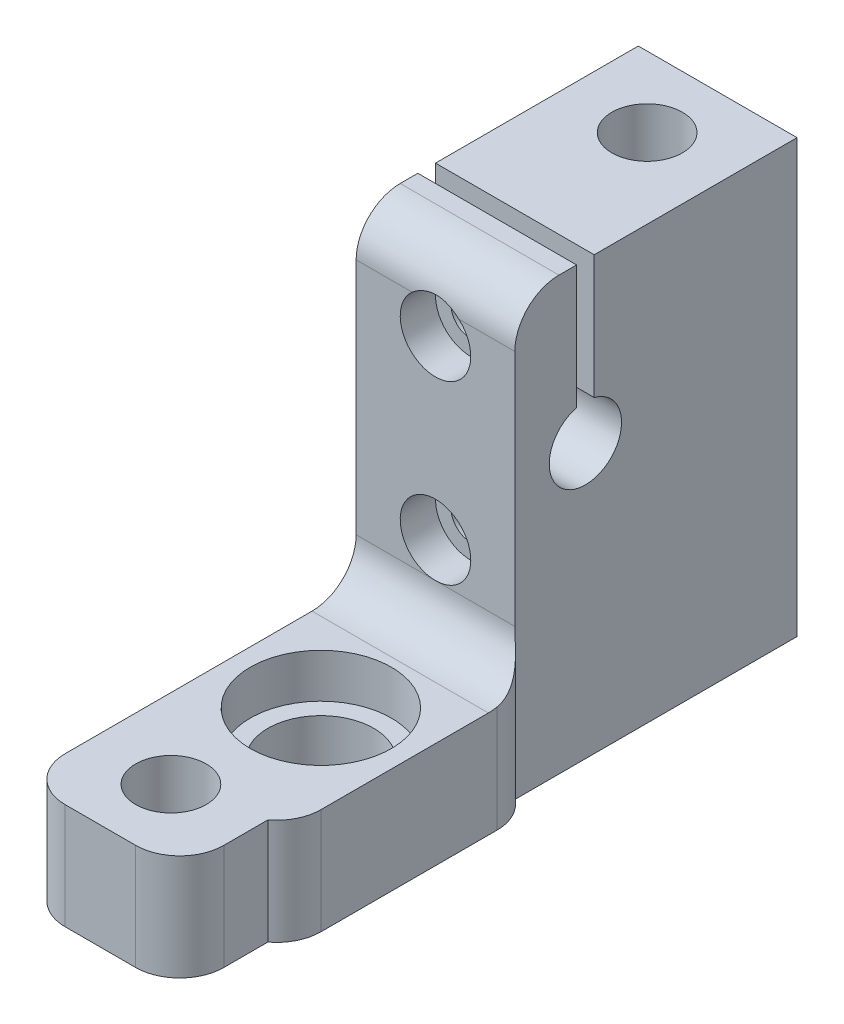
SolidWorks part; units mm, degrees
ref_plane "Спереди" through (0, 0, 0) normal (0, 0, 1) x (1, 0, 0)
ref_plane "Сверху" through (0, 0, 0) normal (0, 1, 0) x (1, 0, 0)
ref_plane "Справа" through (0, 0, 0) normal (1, 0, 0) x (0, 0, -1)
sketch "Эскиз2" plane through (0, 0, 0) normal (0, 1, 0) x (1, 0, 0)
  line L1 (-9, 16) -> (9, 16)
  line L2 (-9, 16) -> (-9, -16)
  line L3 (-9, -16) -> (9, -16)
  line L4 (9, 16) -> (9, -16)
  line L5 (-9, 16) -> (9, -16) construction
  line L6 (-9, -16) -> (9, 16) construction
  point P0 (0, 0)
  dimension "D1" = 32
  dimension "D2" = 18
extrude "Бобышка-Вытянуть1" add sketch "Эскиз2" along normal blind 49
sketch "Эскиз3" plane through (9, 0, -3.2795) normal (1, 0, 0) x (0, 0, -1)
  line L0 (12.7205, 49) -> (12.7205, 0) construction
  line L2 (-19.2795, 0) -> (12.7205, 0) construction
  circle A0 centre (-11.2795, 31) radius 4.1
  dimension "D1" = 8.2
  dimension "D2" = 31
  dimension "D3" = 24
extrude "Вырез-Вытянуть1" cut sketch "Эскиз3" against normal blind 27.3
sketch "Эскиз16" plane through (0, 0, 0) normal (0, -1, 0) x (1, 0, 0)
  line L1 (11, 16) -> (-9, 16)
  line L2 (11, 16) -> (11, 44)
  line L3 (11, 44) -> (-9, 44)
  line L4 (-9, 16) -> (-9, 44)
  dimension "D1" = 20
  dimension "D2" = 28
extrude "Бобышка-Вытянуть3" add sketch "Эскиз16" against normal blind 12
sketch "Эскиз17" plane through (0, 0, 16) normal (0, 0, 1) x (1, 0, 0)
  line L0 (-9, 49) -> (9, 49) construction
  circle A0 centre (0, 41) radius 2.25
  circle A1 centre (0, 21) radius 2.25
  point P5 (0, 49)
  dimension "D1" = 4.5
  dimension "D2" = 8
  dimension "D3" = 20
extrude "Вырез-Вытянуть3" cut sketch "Эскиз17" against normal blind 66
sketch "Эскиз18" plane through (0, 0, -16) normal (0, 0, -1) x (-1, 0, 0)
  line L1 (3, 5) -> (-3, 5)
  line L2 (3, 5) -> (3, 14)
  line L3 (3, 14) -> (-3, 14)
  line L4 (-3, 5) -> (-3, 14)
  line L5 (3, 28) -> (-3, 28)
  line L6 (3, 28) -> (3, 34)
  line L7 (3, 34) -> (-3, 34)
  line L8 (-3, 28) -> (-3, 34)
  line L9 (-9, 0) -> (9, 0) construction
  circle A0 centre (0, 21) radius 2.25 construction
  circle A1 centre (0, 41) radius 2.25 construction
  point P8 (0, 5)
  point P12 (0, 0)
  dimension "D1" = 6
  dimension "D2" = 5
  dimension "D3" = 7
  dimension "D4" = 7
  dimension "D5" = 7
extrude "Бобышка-Вытянуть4" add sketch "Эскиз18" along normal blind 4
sketch "Эскиз19" plane through (0, 0, 16) normal (0, 0, 1) x (1, 0, 0)
  circle A0 centre (0, 21) radius 4
  circle A1 centre (0, 41) radius 4
  dimension "D1" = 8
extrude "Вырез-Вытянуть4" cut sketch "Эскиз19" against normal blind 4
sketch "Эскиз20" plane through (0, 12, 0) normal (0, 1, 0) x (1, 0, 0)
  line L1 (9, 16) -> (-9, 16) construction
  line L2 (11, -16) -> (11, -44) construction
  circle A0 centre (1, -30) radius 8
  circle A1 centre (1, -30) radius 6
  dimension "D1" = 16
  dimension "D2" = 12
  dimension "D3" = 46
  dimension "D4" = 10
sketch "Эскиз23" plane through (0, 0, 0) normal (0, -1, 0) x (1, 0, 0)
  line L0 (-9, -16) -> (-9, 44) construction
  line L1 (9, 44) -> (-9, 44)
  line L2 (9, 44) -> (9, 54)
  line L3 (9, 54) -> (-9, 54)
  line L4 (-9, 44) -> (-9, 54)
  line L5 (9, 16) -> (9, -16) construction
  line L6 (11, 44) -> (-9, 44) construction
  dimension "D1" = 10
extrude "Бобышка-Вытянуть5" add sketch "Эскиз23" against normal up to surface (12 mm away) up to face at (2.6, 12, 27.2)
sketch "Эскиз4" plane through (0, 0, 0) normal (0, -1, 0) x (1, 0, 0)
  line L0 (9, -16) -> (-9, -16) construction
  line L2 (-9, 54) -> (9, 54) construction
  circle A0 centre (0, 46) radius 2.25
  circle A1 centre (0, -8) radius 2.25
  dimension "D3" = 4.5
  dimension "D1" = 8
  dimension "D2" = 8
extrude "Вырез-Вытянуть2" cut sketch "Эскиз4" against normal through all
sketch "Эскиз8" plane through (0, 0, 0) normal (0, -1, 0) x (1, 0, 0)
  line L0 (9, -16) -> (-9, -16) construction
  line L1 (-3, 0) -> (3, 0)
  line L2 (-3, 0) -> (-3, 38)
  line L3 (-3, 38) -> (3, 38)
  line L4 (3, 0) -> (3, 38)
  line L6 (3, 34.8874) -> (-3, 34.8874)
  line L7 (3, 34.8874) -> (3, 24.7217)
  line L8 (3, 24.7217) -> (-3, 24.7217)
  line L9 (-3, 34.8874) -> (-3, 24.7217)
  circle A0 centre (0, -8) radius 2.25 construction
  circle A1 centre (0, 46) radius 2.25 construction
  point P0 (0, -11.3393)
  point P6 (0, 0)
  point P9 (0, -16)
  dimension "D2" = 8
  dimension "D3" = 8
  dimension "D1" = 6
extrude "Вырез-Вытянуть5" cut sketch "Эскиз20" against normal blind 5
extrude "Бобышка-Вытянуть7" add sketch "Эскиз8" along normal blind 4 contours L6 L4 L3 L2 | L4 L8 L2 L1 region at (0, 0, 12.3608) region at (0, 0, 36.4437)
extrude "Вырез-Вытянуть7" cut sketch "Эскиз20<4>" against normal blind 25 contours A1 region at (1, 12, 30)
sketch "Эскиз20<4>" plane through (0, 12, 0) normal (0, 1, 0) x (1, 0, 0) same geometry as "Эскиз20"
fillet "Скругление1" radius 5 2 edges at (11, 6, 44) (11, 6, 16)
fillet "Скругление2" radius 5 4 edges at (0, 12, 16) (0, 49, 16) (9, 6, 54) (-9, 6, 54)
sketch "Эскиз24" plane through (9, 0, 0) normal (1, 0, 0) x (0, 0, -1)
  line L0 (-11, 49) -> (16, 49) construction
  line L1 (-7, 49) -> (-9, 49)
  line L2 (-7, 49) -> (-7, 31)
  line L3 (-7, 31) -> (-9, 31)
  line L4 (-9, 49) -> (-9, 31)
  circle A0 centre (-8, 31) radius 4.1 construction
  point P6 (-8, 31)
  dimension "D1" = 2
extrude "Вырез-Вытянуть8" cut sketch "Эскиз24" against normal blind 23
sketch "Эскиз25" plane through (0, 49, 0) normal (0, 1, 0) x (1, 0, 0)
  circle A0 centre (0, 8) radius 4
  circle A1 centre (0, -46) radius 4
  circle A2 centre (0, -46) radius 2.25 construction
  dimension "D1" = 8
extrude "Вырез-Вытянуть9" cut sketch "Эскиз25" against normal blind 45
